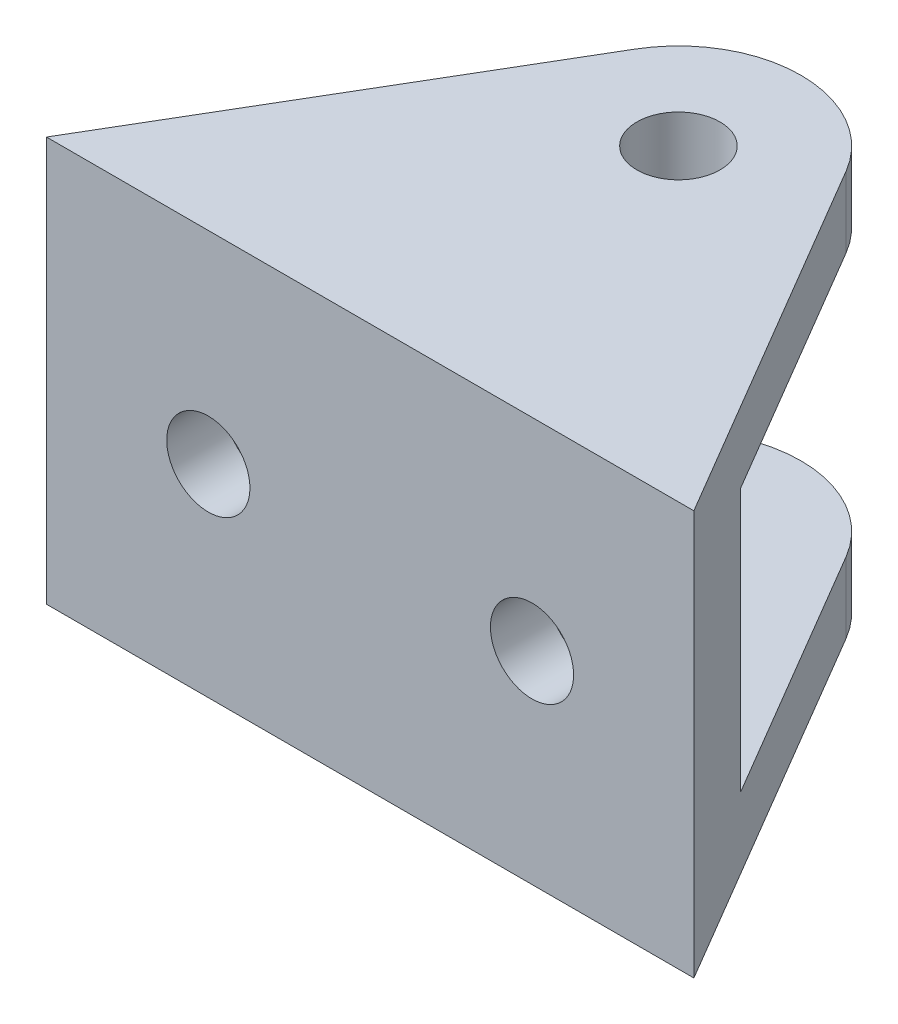
SolidWorks part; units mm, degrees
material "6061-T6 (SS)"
ref_plane "X-Y Datum" through (0, 0, 0) normal (0, 0, 1) x (1, 0, 0)
ref_plane "X-Z Datum" through (0, 0, 0) normal (0, 1, 0) x (1, 0, 0)
ref_plane "Y-Z Datum" through (0, 0, 0) normal (1, 0, 0) x (0, 0, -1)
sketch "Sketch1" plane through (0, 0, 0) normal (1, 0, 0) x (0, 0, -1)
  line L0 (0, 0) -> (0, 31.75)
  line L1 (0, 31.75) -> (43.2881, 31.75)
  line L2 (43.2881, 31.75) -> (43.2881, 26.2001)
  line L3 (43.2881, 26.2001) -> (8.89, 26.2001)
  line L4 (8.89, 26.2001) -> (8.89, 5.5499)
  line L5 (8.89, 5.5499) -> (43.2881, 5.5499)
  line L6 (43.2881, 5.5499) -> (43.2881, 0)
  line L7 (43.2881, 0) -> (0, 0)
  line L8 (30.5881, 31.75) -> (30.5881, 0) construction
  dimension "D1" = 20.6502
  dimension "D2" = 31.75
  dimension "D3" = 12.7
  dimension "D4" = 8.89
extrude "Boss-Extrude1" add sketch "Sketch1" along normal blind 50.8
sketch "Sketch2" plane through (0, 0, -8.89) normal (0, 0, -1) x (-1, 0, 0)
  line L0 (-50.8, 15.875) -> (0, 15.875) construction
  line L1 (-50.8, 5.5499) -> (-50.8, 26.2001) construction
  line L2 (0, 5.5499) -> (0, 26.2001) construction
  line L3 (-25.4, 5.5499) -> (-25.4, 26.2001) construction
  line L4 (-50.8, 5.5499) -> (0, 5.5499) construction
  line L5 (-50.8, 26.2001) -> (0, 26.2001) construction
  point P6 (-38.1, 15.875)
  point P7 (-12.7, 15.875)
  dimension "D1" = 25.4
  dimension "D2" = 12.7
hole_wizard "CBORE for 1/4 Binding Head Machine Screw1" positions "Sketch2" profile "Sketch3" counterbore size "1/4" standard "ANSI Inch" end condition through all
sketch "Sketch3" plane through (12.7, 15.875, -8.89) normal (1, 0, 0) x (0, 1, 0)
  line L0 (0, 0) -> (0, 8.89)
  line L1 (0, 8.89) -> (3.2639, 8.89)
  line L3 (3.2639, 8.89) -> (3.2639, 4.318)
  line L4 (3.2639, 4.318) -> (7.1437, 4.318)
  line L5 (7.1437, 4.318) -> (7.1437, 0)
  line L7 (7.1437, 0) -> (0, 0)
  line L11 (0, -6.35) -> (0, 107.95) construction
  dimension "Thru Hole Dia." = 6.5278
  dimension "Thru Hole Depth" = 8.89
  dimension "C'Bore Dia." = 14.2875
  dimension "C'Bore Depth" = 4.318
sketch "Sketch4" plane through (0, 0, 0) normal (0, -1, 0) x (1, 0, 0)
  line L0 (25.4, 0) -> (25.4, -43.2881) construction
  line L1 (50.8, 0) -> (0, 0) construction
  line L2 (50.8, -43.2881) -> (0, -43.2881) construction
  line L3 (17.1156, -29.0671) -> (0, 0)
  line L4 (33.6844, -29.0671) -> (50.8, 0)
  line L5 (0, 0) -> (0, -43.2881)
  line L6 (0, -43.2881) -> (50.8, -43.2881)
  line L7 (50.8, -43.2881) -> (50.8, 0)
  circle A0 centre (25.4, -24.189) radius 3.2639
  arc A1 (17.1156, -29.0671) -> (33.6844, -29.0671) centre (25.4, -24.189) ccw
  dimension "D1" = 6.5278
  dimension "D2" = 6.35
extrude "Cut-Extrude1" cut sketch "Sketch4" against normal up to surface (31.75 mm away) up to face at (25.4, 31.75, -21.644)
